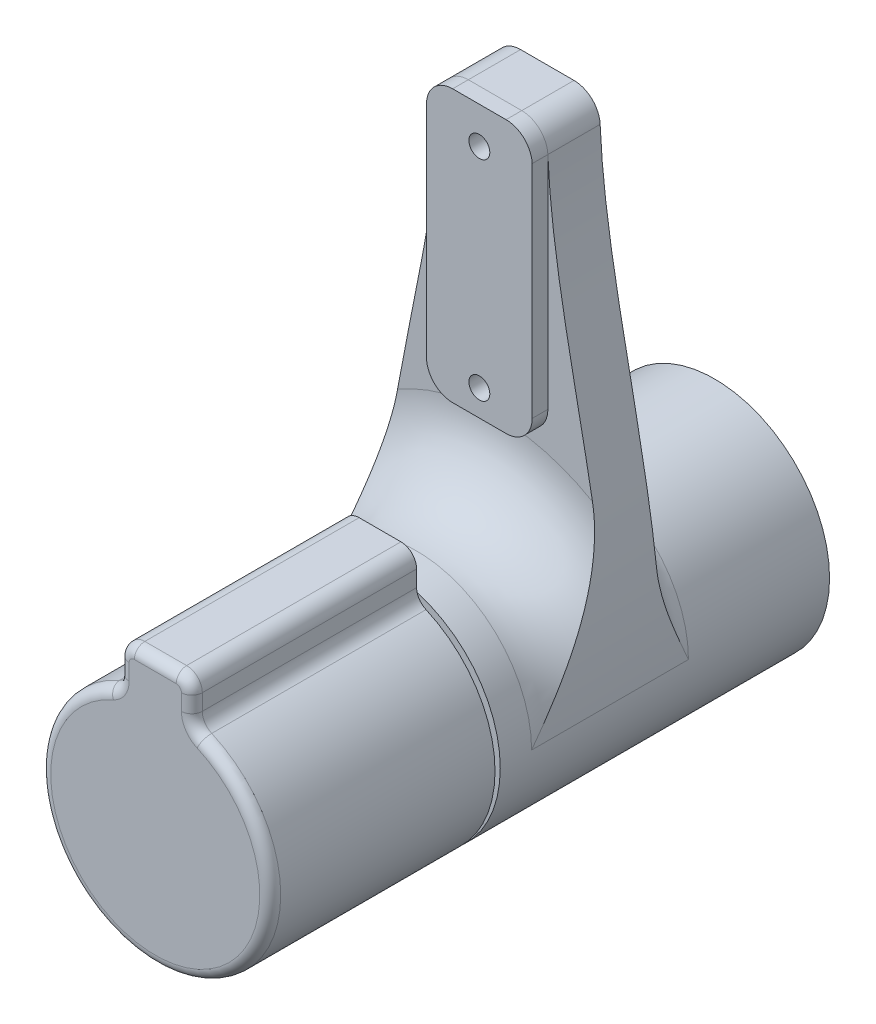
SolidWorks part; units mm, degrees
ref_plane "Front Plane" through (0, 0, 0) normal (0, 0, 1) x (1, 0, 0)
ref_plane "Top Plane" through (0, 0, 0) normal (0, 1, 0) x (1, 0, 0)
ref_plane "Right Plane" through (0, 0, 0) normal (1, 0, 0) x (0, 0, -1)
sketch "Sketch1" plane through (0, 0, 0) normal (0, 0, 1) x (1, 0, 0)
  circle A0 centre (0, 0) radius 18
  circle A1 centre (0, 0) radius 11
  circle A2 centre (0, 14) radius 1.5
  circle A3 centre (14, 0) radius 1.5
  circle A4 centre (0, -14) radius 1.5
  circle A5 centre (-14, 0) radius 1.5
  point P15 (0, 0)
  dimension "D1" = 36
  dimension "D2" = 22
  dimension "D3" = 3
  dimension "D4" = 14
  dimension "D5" = 4
extrude "Boss-Extrude1" add sketch "Sketch1" along normal blind 3
sketch "Sketch2" plane through (0, 0, 3) normal (0, 0, 1) x (1, 0, 0)
  circle A0 centre (0, 0) radius 22
  circle A1 centre (0, 0) radius 18 construction
  circle A2 centre (0, 0) radius 18
  dimension "D1" = 44
extrude "Boss-Extrude2" add sketch "Sketch2" along normal blind 60 and the other way through all
sketch "Sketch3" plane through (0, 0, 0) normal (0, 1, 0) x (1, 0, 0)
  line L0 (-22, 0) -> (-22, -63) construction
  line L1 (-22, -32) -> (22, -32)
  line L2 (-22, -32) -> (-22, -42)
  line L3 (-22, -42) -> (22, -42)
  line L4 (22, -32) -> (22, -42)
  line L5 (22, -63) -> (22, 0) construction
  line L6 (22, 0) -> (-22, 0) construction
  dimension "D1" = 10
  dimension "D2" = 32
extrude "Boss-Extrude3" add sketch "Sketch3" along normal blind 60 and the other way up to surface from offset 30 other way up to face at (22, 0, 0)
sketch "Sketch5" plane through (0, 0, 42) normal (0, 0, 1) x (1, 0, 0)
  line L0 (-10, 90) -> (10, 90)
  line L1 (-22, 90) -> (22, 90) construction
  line L2 (-22, 0) -> (-22, 90) construction
  line L3 (-22, 36.8481) -> (-22, -36.8491) construction
  line L4 (-10, 113.008) -> (-10, 66.992) construction
  line L5 (0, 90) -> (0, 0) construction
  line L6 (-22, 0) -> (-62.3653, 12.5619)
  line L7 (-62.3653, 12.5619) -> (-32.5319, 92.6174)
  line L8 (-32.5319, 92.6174) -> (30.2832, 92.6174)
  line L9 (30.2832, 92.6174) -> (54.1199, -5.1283)
  line L10 (54.1199, -5.1283) -> (22, 0)
  circle A0 centre (0, 0) radius 22 construction
  spline S0 degree 3 poles (-22, 0) (-22, 30.7072) (-10, 61.2401) (-10, 90) knots 0 0 0 0 1 1 1 1
  spline S1 degree 3 poles (22, 0) (22, 30.7072) (10, 61.2401) (10, 90) knots 0 0 0 0 1 1 1 1
  point P5 (0, 90)
  dimension "D1" = 20
extrude "Cut-Extrude1" cut sketch "Sketch5" against normal blind 60
fillet "Fillet1" radius 15 1 edges at (0, 22, 42)
fillet "Fillet2" radius 5 1 edges at (0, 22, 32)
sketch "Sketch6" plane through (0, 0, 42) normal (0, 0, 1) x (1, 0, 0)
  circle A0 centre (0, 83) radius 2
  circle A1 centre (0, 43) radius 2
  dimension "D3" = 4
  dimension "D1" = 43
  dimension "D2" = 40
extrude "Cut-Extrude2" cut sketch "Sketch6" against normal through all
fillet "Fillet3" radius 5 2 edges at (10, 90, 37) (-10, 90, 37)
sketch "Sketch7" plane through (0, 0, 63) normal (0, 0, 1) x (1, 0, 0)
  line L1 (-4, 10) -> (4, 10)
  line L2 (-4, 10) -> (-4, 26)
  line L3 (-4, 26) -> (4, 26)
  line L4 (4, 10) -> (4, 26)
  line L5 (-4, 10) -> (4, 26) construction
  line L6 (-4, 26) -> (4, 10) construction
  line L7 (-7, 15) -> (7, 15)
  line L8 (-7, 15) -> (-7, 29)
  line L9 (-7, 29) -> (7, 29)
  line L10 (7, 15) -> (7, 29)
  line L11 (-7, 15) -> (7, 29) construction
  line L12 (-7, 29) -> (7, 15) construction
  circle A0 centre (0, 0) radius 18 construction
  circle A1 centre (0, 0) radius 22
  circle A2 centre (0, 0) radius 22
  circle A3 centre (0, 0) radius 18
  point P6 (0, 18)
  point P11 (0, 22)
  circle M11 centre (0, 0) radius 22
  circle M12 centre (0, 0) radius 18
  dimension "D2" = 3
  dimension "D3" = 3
  dimension "D4" = 8
  dimension "D5" = 8
  dimension "D1" = 0
extrude "Boss-Extrude4" add sketch "Sketch7" along normal blind 40 from offset 1 separate body contours L10 L8 M12 M11 | L8 L2 M12 M11 | L10 L4 M12 M11 | L10 L9 L8 L2 L3 L4 M11 region at (-5.5114, 19.1955, 63) region at (5.5114, 19.1955, 63) region at (-5.5543, 21.4547, 63) region at (-10.2894, -15.5119, 63)
sketch "Sketch8" plane through (0, 0, 104) normal (0, 0, 1) x (1, 0, 0)
  line L3 (7, 20.8567) -> (7, 29)
  line L4 (7, 29) -> (-7, 29)
  line L5 (-7, 29) -> (-7, 20.8567)
  line L6 (7, 20.8567) -> (7, 29)
  line L7 (7, 29) -> (-7, 29)
  line L8 (-7, 29) -> (-7, 20.8567)
  arc A1 (-7, 20.8567) -> (7, 20.8567) centre (0, 0) ccw
  arc A2 (-7, 20.8567) -> (7, 20.8567) centre (0, 0) ccw
  dimension "D1" = 0
extrude "Boss-Extrude5" add sketch "Sketch8" along normal blind 3
fillet "Fillet4" radius 3 8 edges at (-4, 26, 84) (4, 26, 84) (-7, 29, 85.5) (7, 29, 85.5) (-4, 17.5499, 84) (4, 17.5499, 84) (7, 20.8567, 85.5) (-7, 20.8567, 85.5)
fillet "Fillet5" radius 2 16 edges at (-7.49, 21.2697, 107) (-7, 24.4564, 107) (-6.1213, 28.1213, 107) (0, 29, 107) (6.1213, 28.1213, 107) (7, 24.4564, 107) (7.49, 21.2697, 107) (4.5505, 18.0669, 104) (4, 21.3995, 104) (3.1213, 25.1213, 104) (0, 26, 104) (-3.1213, 25.1213, 104) (-4, 21.3995, 104) (-4.5505, 18.0669, 104) (0, -22, 107) (0, -18, 104)
sketch "Sketch9" plane through (0, 0, 42) normal (0, 0, 1) x (1, 0, 0)
  line L0 (-5.1106, 90) -> (5.1106, 90) construction
  line L1 (-5.1106, 90) -> (5.1106, 90)
  line L2 (-10.1059, 85.2162) -> (-10.1059, 43)
  line L3 (-5.1059, 38) -> (5.1059, 38)
  line L4 (10.1059, 43) -> (10.1059, 85.2162)
  arc A0 (10.1059, 85.2162) -> (5.1106, 90) centre (5.1106, 85) ccw construction
  arc A1 (-5.1106, 90) -> (-10.1059, 85.2162) centre (-5.1106, 85) ccw construction
  arc A2 (10.1059, 85.2162) -> (5.1106, 90) centre (5.1106, 85) ccw
  arc A3 (-5.1106, 90) -> (-10.1059, 85.2162) centre (-5.1106, 85) ccw
  circle A4 centre (0, 83) radius 2 construction
  circle A5 centre (0, 43) radius 2 construction
  circle A6 centre (0, 83) radius 2
  circle A7 centre (0, 43) radius 2
  arc A8 (5.1059, 38) -> (10.1059, 43) centre (5.1059, 43) ccw
  arc A9 (-10.1059, 43) -> (-5.1059, 38) centre (-5.1059, 43) ccw
  dimension "D2" = 5
  dimension "D1" = 5
extrude "Boss-Extrude6" add sketch "Sketch9" along normal blind 3 separate body
